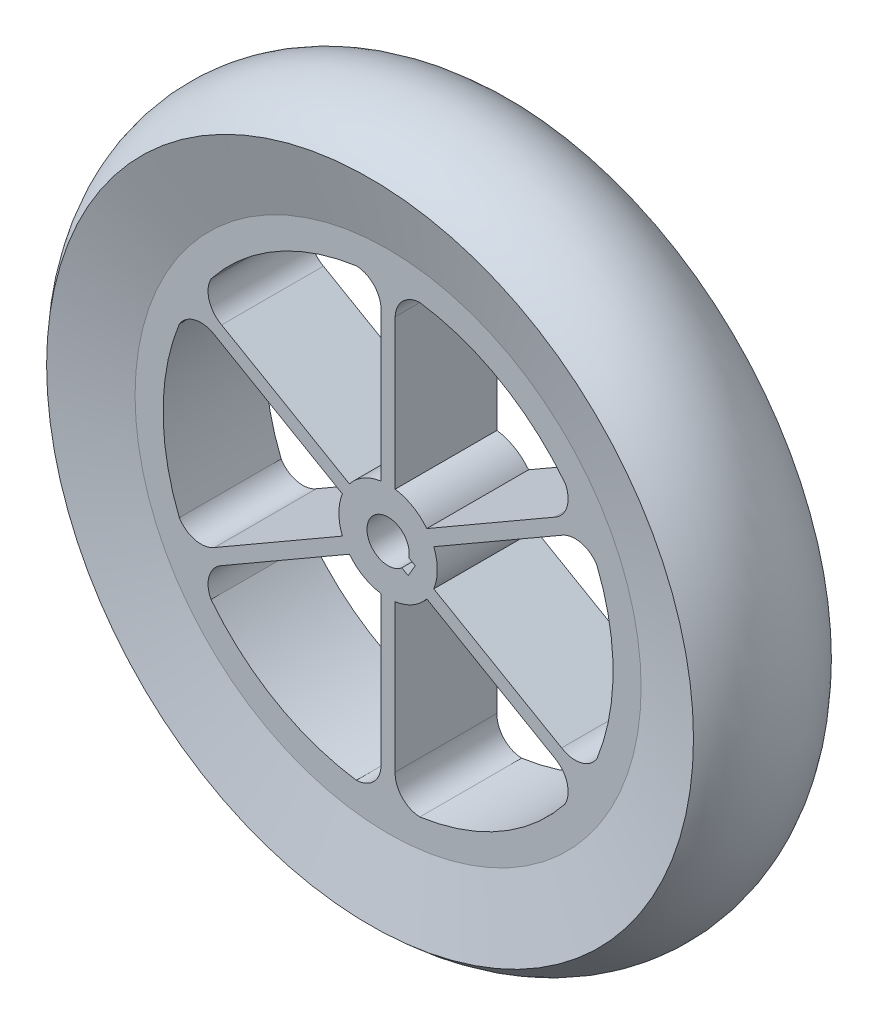
SolidWorks part; units mm, degrees
ref_plane "前视基准面" through (0, 0, 0) normal (0, 0, 1) x (1, 0, 0)
ref_plane "上视基准面" through (0, 0, 0) normal (0, 1, 0) x (1, 0, 0)
ref_plane "右视基准面" through (0, 0, 0) normal (1, 0, 0) x (0, 0, -1)
sketch "Sketch1" plane through (0, 0, 0) normal (0, 0, 1) x (1, 0, 0)
  line L0 (-3.175, 21.997) -> (-3.175, 89.4141)
  line L1 (3.175, 21.997) -> (3.175, 89.4141)
  line L2 (0, 101.6) -> (0, 22.225) construction
  line L3 (20.6375, 8.2489) -> (79.0224, 41.9574)
  line L4 (17.4625, 13.7482) -> (75.8474, 47.4567)
  line L5 (17.4625, -13.7482) -> (75.8474, -47.4567)
  line L6 (20.6375, -8.2489) -> (79.0224, -41.9574)
  line L7 (-3.175, -21.997) -> (-3.175, -89.4141)
  line L8 (3.175, -21.997) -> (3.175, -89.4141)
  line L9 (-20.6375, -8.2489) -> (-79.0224, -41.9574)
  line L10 (-17.4625, -13.7482) -> (-75.8474, -47.4567)
  line L11 (-17.4625, 13.7482) -> (-75.8474, 47.4567)
  line L12 (-20.6375, 8.2489) -> (-79.0224, 41.9574)
  line L13 (0, 0) -> (3.175, 21.997) construction
  line L14 (0, 0) -> (20.6375, 8.2489) construction
  line L15 (17.4625, -13.7482) -> (20.6375, -8.2489) construction
  line L16 (9.0591, -8.8964) -> (12.2341, -3.3972)
  line L17 (12.2341, -3.3972) -> (9.3646, -1.7405)
  line L18 (9.0591, -8.8964) -> (6.1896, -7.2398)
  circle A0 centre (0, 0) radius 101.6
  circle A1 centre (0, 0) radius 158.75
  circle A2 centre (0, 0) radius 22.225
  arc A3 (3.175, 88.6419) -> (14.3434, 100.5824) centre (14.7294, 89.028) cw
  arc A4 (-3.175, 88.6419) -> (-14.3434, 100.5824) centre (-14.7294, 89.028) ccw
  arc A5 (75.1786, 47.0706) -> (79.9353, 62.7129) centre (69.7358, 57.2701) ccw
  arc A6 (78.3536, 41.5713) -> (94.2786, 37.8695) centre (84.4652, 31.7579) cw
  arc A7 (78.3536, -41.5713) -> (94.2786, -37.8695) centre (84.4652, -31.7579) ccw
  arc A8 (75.1786, -47.0706) -> (79.9353, -62.7129) centre (69.7358, -57.2701) cw
  arc A9 (3.175, -88.6419) -> (14.3434, -100.5824) centre (14.7294, -89.028) ccw
  arc A10 (-3.175, -88.6419) -> (-14.3434, -100.5824) centre (-14.7294, -89.028) cw
  arc A11 (-75.1786, -47.0706) -> (-79.9353, -62.7129) centre (-69.7358, -57.2701) ccw
  arc A12 (-78.3536, -41.5713) -> (-94.2786, -37.8695) centre (-84.4652, -31.7579) cw
  arc A13 (-78.3536, 41.5713) -> (-94.2786, 37.8695) centre (-84.4652, 31.7579) ccw
  arc A14 (-75.1786, 47.0706) -> (-79.9353, 62.7129) centre (-69.7358, 57.2701) cw
  circle A15 centre (0, 0) radius 9.525
  dimension "D1" = 317.5
  dimension "D2" = 203.2
  dimension "D6" = 44.45
  dimension "D9" = 19.05
  dimension "D3" = 3.175
  dimension "D4" = 3.175
  dimension "D5" = 6
  dimension "D7" = 60
  dimension "D8" = 22.225
  dimension "D10" = 12.2936
  dimension "D11" = 6.35
extrude "Boss-Extrude1" add sketch "Sketch1" along normal blind 45.974 contours A1 A0 | A2 A0 | A2 | A2 A0 | L2 A0 A4 L0 A2 | A0 L2 A2 L1 A3 | A2 A0 | A2 A0 | A2 A0 region at (0, 66.3483, 0) region at (0, 21.5964, 0) region at (-57.4593, 33.1742, 0) region at (57.4593, 33.1742, 0) region at (-57.4593, -33.1742, 0) region at (57.4593, -33.1742, 0) region at (0, -66.3483, 0) region at (-154.2599, 0, 0)
sketch "Sketch2" plane through (0, 0, 0) normal (0, 1, 0) x (1, 0, 0)
  line L0 (146.05, 8.1506) -> (114.2567, 0)
  line L1 (158.75, 0) -> (-158.75, 0) construction
  line L3 (114.2567, 0) -> (152.3567, 0)
  line L4 (146.05, -54.1246) -> (114.2567, -45.974)
  line L6 (-158.75, -45.974) -> (158.75, -45.974) construction
  line L7 (114.2567, -45.974) -> (152.3567, -45.974)
  line L8 (0, 0) -> (0, 35.1972) construction
  line L9 (152.3567, -45.974) -> (158.75, -45.974)
  line L10 (158.75, -45.974) -> (158.75, 0)
  line L11 (158.75, 0) -> (152.3567, 0)
  arc A0 (146.05, 8.1506) -> (146.05, -54.1246) centre (114.2288, -22.987) cw
  dimension "D1" = 38.1
  dimension "D2" = 38.1
  dimension "D3" = 12.7
revolve "Cut-Revolve1" cut sketch "Sketch2" angle 360 mid plane about L8 region at (156.8582, 0, 40.313) region at (156.8582, 0, 5.661)
revolve "Revolve2" add sketch "Sketch2<6>" angle 360 mid plane about L8 region at (137.708, 0, -2.7356) region at (137.708, 0, 48.7096)
sketch "Sketch2<6>" plane through (0, 0, 0) normal (0, 1, 0) x (1, 0, 0) same geometry as "Sketch2"
